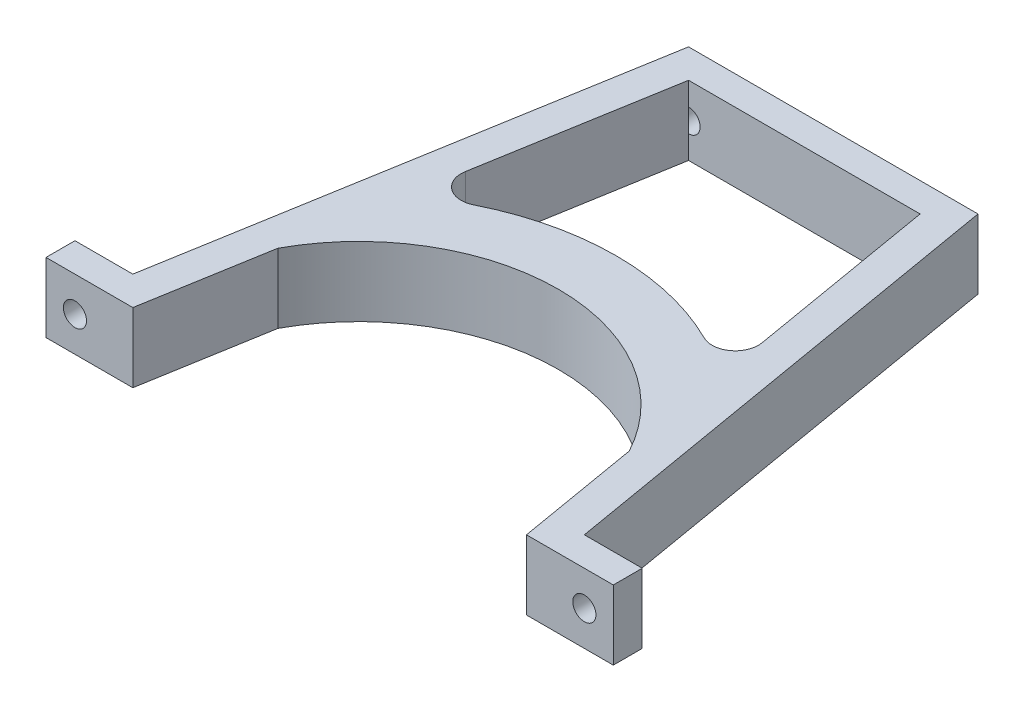
SolidWorks part; units mm, degrees
ref_plane "Front Plane" through (0, 0, 0) normal (0, 0, 1) x (1, 0, 0)
ref_plane "Top Plane" through (0, 0, 0) normal (0, 1, 0) x (1, 0, 0)
ref_plane "Right Plane" through (0, 0, 0) normal (1, 0, 0) x (0, 0, -1)
sketch "Sketch1" plane through (0, 0, 0) normal (0, 1, 0) x (1, 0, 0)
  line L5 (49, 0) -> (39, 0)
  line L6 (0, 0) -> (0, 82) construction
  line L7 (-25, 82) -> (25, 82)
  line L8 (25, 82) -> (39, 0)
  line L9 (49, 0) -> (49, -5)
  line L10 (49, -5) -> (34, -5)
  line L11 (-25.6244, 44.0571) -> (-34, -5)
  line L12 (0, -5) -> (0, 0) construction
  line L13 (0, 82) -> (0, 77) construction
  line L14 (-20, 77) -> (20, 77)
  line L15 (20, 77) -> (25.6244, 44.0571)
  line L16 (39, 0) -> (49, 0)
  line L17 (-39, 0) -> (-49, 0)
  line L18 (-20, 77) -> (-25.6244, 44.0571)
  line L19 (-49, -5) -> (-34, -5)
  line L20 (-49, 0) -> (-49, -5)
  line L21 (-25, 82) -> (-39, 0)
  line L22 (-49, 0) -> (-39, 0)
  line L23 (25.6244, 44.0571) -> (34, -5)
  arc A0 (30.3434, 16.4173) -> (-30.3434, 16.4173) centre (0, 0) ccw
  arc A1 (19.8933, 39.8059) -> (-19.8933, 39.8059) centre (0, 0) ccw
  arc A2 (19.8933, 39.8059) -> (25.6244, 44.0571) centre (21.6815, 43.3839) ccw
  arc A3 (39.1386, 21.176) -> (-39.1386, 21.176) centre (0, 0) ccw construction
  arc A4 (-19.8933, 39.8059) -> (-25.6244, 44.0571) centre (-21.6815, 43.3839) cw
  dimension "D1" = 50
  dimension "D2" = 10
  dimension "D3" = 4
  dimension "D4" = 87
  dimension "D5" = 49
extrude "Boss-Extrude1" add sketch "Sketch1" along normal blind 12 contours A1 A4 L11 A0 L23 A2 | L15 L23 L10 L9 L5 L8 L7 L21 L17 L20 L19 L11 L18 L14 region at (47.6895, 0, 2.5) region at (0, 0, -35.1373)
sketch "Sketch2" plane through (0, 0, 0) normal (0, 0, 1) x (1, 0, 0)
  circle A0 centre (-44, 6) radius 2
  circle A1 centre (44, 6) radius 2
  circle A2 centre (-20, 6) radius 2
  circle A3 centre (20, 6) radius 2
extrude "Cut-Extrude4" cut sketch "Sketch2" along normal blind 12 contours A1 | A0 region at (44, 6, 0)
cosmetic thread "Cosmetic Thread1" parameters "D1"=5, "D2"=5
cosmetic thread "Cosmetic Thread2" parameters "D1"=5, "D2"=5
extrude "Cut-Extrude5" cut sketch "Sketch2<3>" against normal blind 12 from offset 77 contours A2 | A3 region at (-20, 6, 0) region at (20, 6, 0) offset against normal yes
sketch "Sketch2<3>" plane through (0, 0, 0) normal (0, 0, 1) x (1, 0, 0) same geometry as "Sketch2"
cosmetic thread "Cosmetic Thread3" parameters "D1"=5, "D2"=5
cosmetic thread "Cosmetic Thread4" parameters "D1"=5, "D2"=5
